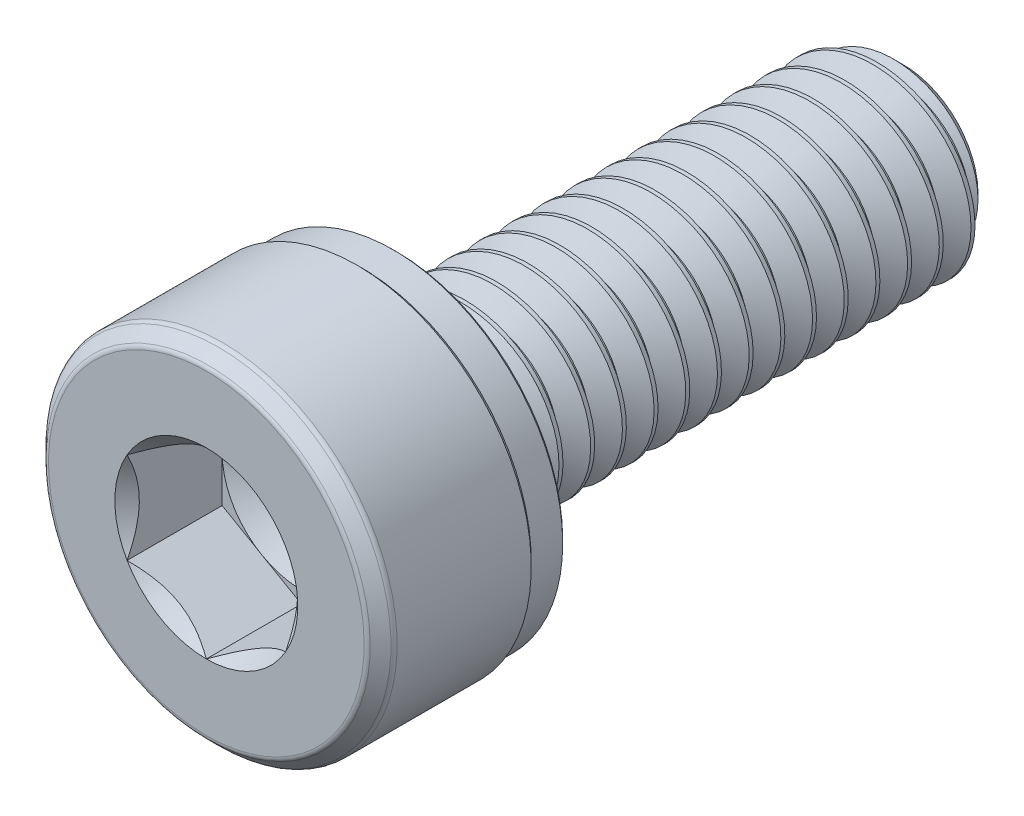
SolidWorks part; units mm, degrees
ref_plane "Front Plane" through (0, 0, 0) normal (0, 0, 1) x (1, 0, 0)
ref_plane "Top Plane" through (0, 0, 0) normal (0, 1, 0) x (1, 0, 0)
ref_plane "Right Plane" through (0, 0, 0) normal (1, 0, 0) x (0, 0, -1)
sketch "Sketch1" plane through (0, 0, 0) normal (1, 0, 0) x (0, 0, -1)
  line L0 (-5.5, 0) -> (5.5, 0) construction
  line L1 (-5.5, 0) -> (-5.5, 2.75) construction
  line L2 (-5.5, 2.75) -> (-2.5, 2.75) construction
  line L3 (-2.5, 2.75) -> (-2.5, 1.5) construction
  line L4 (-2.5, 1.5) -> (5.1752, 1.5) construction
  line L5 (5.4688, 1.5541) -> (5.7188, 1.1211) construction
  line L6 (5.7188, 1.1211) -> (5.9688, 1.5541) construction
  line L7 (5.9688, 1.5541) -> (5.4688, 1.5541) construction
  line L8 (5.1752, 1.5) -> (5.5, 1.1752) construction
  line L9 (5.5, 1.1752) -> (5.5, 0) construction
  line L10 (5.5, 1.5) -> (5.9375, 1.5) construction
  line L11 (5.7188, 1.5541) -> (5.7188, 1.5) construction
  line L12 (5.7188, 1.5) -> (5.7188, 1.1752) construction
  line L13 (5.7188, 1.1752) -> (5.7188, 1.1211) construction
  line L14 (5.6875, 1.1752) -> (5.75, 1.1752) construction
  line L15 (5.4844, 1.5271) -> (5.9531, 1.5271) construction
  line L16 (5.75, 1.1752) -> (5.9531, 1.5271) construction
  line L17 (5.6875, 1.1752) -> (5.4844, 1.5271) construction
  line L18 (-5.5, 1.25) -> (-4, 1.25) construction
  line L19 (-4, 1.25) -> (-4, 0) construction
  line L20 (4.75, 1.5) -> (4.75, -1.5) construction
  point P20 (5.7188, 1.5271)
  point P22 (4.75, -1.5)
  point P28 (4.75, 0)
  point P29 (5.1752, -1.5)
  point P30 (-3.25, 2.75)
  point P31 (-0.5, 0)
  point P33 (3.5, 0)
  dimension "Length" = 8
  dimension "Head Height" = 3
  dimension "D1" = 45
  dimension "Thread Pitch" = 0.5
  dimension "D3" = 0.0625
  dimension "D4" = 0.75
  dimension "D5" = 1.5
  dimension "D2" = 2.25
  dimension "Head Diameter" = 5.5
  dimension "Drive Size" = 2.5
  dimension "Screw Size Decimal Equivalent" = 3
  dimension "D6" = 2
  dimension "D7" = 2
  dimension "Thread Size" = 3
sketch "Sketch3" plane through (0, 0, 0) normal (1, 0, 0) x (0, 0, -1)
  line L0 (-5.5, 2.4901) -> (-5.5, 1.25)
  line L1 (-5.5, 1.25) -> (-4, 1.25)
  line L2 (-4, 1.25) -> (-4, 0)
  line L3 (-4, 0) -> (5.5, 0)
  line L4 (5.5, 0) -> (5.5, 1.1752)
  line L5 (5.5, 1.1752) -> (5.1752, 1.5)
  line L6 (5.1752, 1.5) -> (-2.3125, 1.5)
  line L7 (-2.5, 1.6875) -> (-2.5, 2.75)
  line L8 (-2.5, 2.75) -> (-5.2401, 2.75)
  line L9 (-5.4718, 2.5582) -> (-5.3082, 2.7218)
  line L11 (-5.5, 2.75) -> (-2.5, 2.75) construction
  arc A0 (-5.3082, 2.7218) -> (-5.2401, 2.75) centre (-5.2401, 2.6538) cw
  arc A1 (-5.4718, 2.5582) -> (-5.5, 2.4901) centre (-5.4037, 2.4901) ccw
  arc A6 (-2.3125, 1.5) -> (-2.5, 1.6875) centre (-2.3125, 1.6875) cw
  point P25 (-5.5, 2.53)
  point P33 (-2.5, 1.5)
  dimension "D3" = 0.0963
  dimension "D10" = 0.1875
  dimension "D1" = 45
  dimension "D2" = 0.22
revolve "Revolve1" add sketch "Sketch3" angle 360 about L0
sketch "Sketch4" plane through (0, 0, 5.5) normal (0, 0, 1) x (1, 0, 0)
  line L1 (0, 1.4434) -> (-1.25, 0.7217)
  line L2 (-1.25, 0.7217) -> (-1.25, -0.7217)
  line L3 (-1.25, -0.7217) -> (0, -1.4434)
  line L4 (0, -1.4434) -> (1.25, -0.7217)
  line L5 (1.25, -0.7217) -> (1.25, 0.7217)
  line L6 (1.25, 0.7217) -> (0, 1.4434)
  circle A0 centre (0, 0) radius 1.25 construction
  point P11 (0, -1.4434)
extrude "Cut-Extrude1" cut sketch "Sketch4" against normal up to vertex (1.5 mm away) up to point (0, 1.25, 4)
sketch "Sketch5" plane through (0, 0, 5.5) normal (0, 0, 1) x (1, 0, 0)
  circle A0 centre (0, 0) radius 1.4434
extrude "Cut-Extrude2" cut sketch "Sketch5" against normal up to next (1.5 mm away) draft 45
sketch "Sketch10" plane through (0, 0, 4) normal (0, 0, 1) x (1, 0, 0)
  line L0 (1.25, 0.7217) -> (1.25, -0.7217) construction
  circle A0 centre (0, 0) radius 1.25
extrude "Cut-Extrude3" cut sketch "Sketch10" against normal through all draft 60
sketch "Sketch13" plane through (0, 0, 0) normal (1, 0, 0) x (0, 0, -1)
  line L0 (-2.5, 2.75) -> (-3.123, 2.75)
  line L1 (-3.123, 2.75) -> (-3.0468, 2.6738)
  line L2 (-3.0468, 2.6738) -> (-2.5, 2.6738)
  line L3 (-2.5, 2.6738) -> (-2.5, 2.75)
  dimension "D1" = 0.0762
  dimension "D2" = 45
  dimension "D3" = 0.127
revolve "Cut-Revolve1" cut sketch "Sketch13" angle 360 about L0
chamfer "Chamfer1" distance 0.0508 angle 45 1 edges at (0, -2.6738, 2.5)
sketch "Sketch6" plane through (0, 0, -5.5) normal (0, 0, -1) x (-1, 0, 0)
  circle A0 centre (0, 0) radius 1.5 construction
  circle A1 centre (0, 0) radius 1.5
curve "Helix/Spiral1" pitch 0.5 height 8 radius 1.5 centre (0, 0, -5.5) axis (0, 0, 1) start towards (0, 1, 0)
ref_plane "Plane1" through (0, 0, 2.3125) normal (0, 0, 1) x (1, 0, 0)
sketch "Sketch7" plane through (0, 0, 0) normal (1, 0, 0) x (0, 0, -1)
  line L8 (5.4844, 1.5271) -> (5.9531, 1.5271)
  line L9 (5.9531, 1.5271) -> (5.75, 1.1752)
  line L10 (5.75, 1.1752) -> (5.6875, 1.1752)
  line L11 (5.6875, 1.1752) -> (5.4844, 1.5271)
sweep "Cut-Sweep1" cut profiles "Sketch7" path "Helix/Spiral1"
sketch "Sketch11" plane through (0, 0, 0) normal (1, 0, 0) x (0, 0, -1)
  line L2 (-2.5, 1.5) -> (5.1752, 1.5) construction
  line L4 (-2, 1.5) -> (-0.5, 0)
  line L5 (-5.5, 0) -> (5.5, 0) construction
  line L6 (-0.5, 0) -> (-2.5, 0)
  line L7 (-2.5, 0) -> (-2.5, 2.75) construction
  line L9 (-3.2783, 1.6875) -> (-3.2783, 0)
  line L10 (-3.2783, 0) -> (-2.5, 0)
  line L11 (-2.5, 1.6875) -> (-2.5, 2.75) construction
  line L15 (-2.5, 1.6875) -> (-3.2783, 1.6875)
  line L17 (-2.3125, 1.5) -> (-2, 1.5)
  arc A2 (-2.5, 1.6875) -> (-2.3125, 1.5) centre (-2.3125, 1.6875) ccw construction
  arc A3 (-2.5, 1.6875) -> (-2.3125, 1.5) centre (-2.3125, 1.6875) ccw
  dimension "D3" = 45
  dimension "D1" = 0.5
revolve "Revolve2" add sketch "Sketch11" angle 360 about L0
equation "\"D3@Sketch1\" = \"Thread Pitch@Sketch1\" / 8"
equation "\"D4@Sketch1\"=\"Thread Pitch@Sketch1\" * 1.5"
equation "\"D3@Helix/Spiral1\"=\"Length@Sketch1\""
equation "\"D4@Helix/Spiral1\" = \"Thread Pitch@Sketch1\""
equation "\"D5@Sketch1\"=\"Head Height@Sketch1\"*0.5"
equation "\"D2@Sketch3\"=\"Head Diameter@Sketch1\" /25"
equation "\"D3@Sketch3\"=\"D2@Sketch3\"*0.4375"
equation "\"D2@Sketch1\"=\"Head Height@Sketch1\"*0.75"
equation "\"D1@Sketch11\"=\"Thread Pitch@Sketch1\""
equation "\"D10@Sketch3\"=\"Screw Size Decimal Equivalent@Sketch1\"*0.0625"
equation "\"D6@Sketch1\"=\"D7@Sketch1\""
equation "\"D3@Sketch1\"=\"Thread Pitch@Sketch1\"/8"
equation "\"D7@Sketch1\"=\"Length@Sketch1\"*.25"
